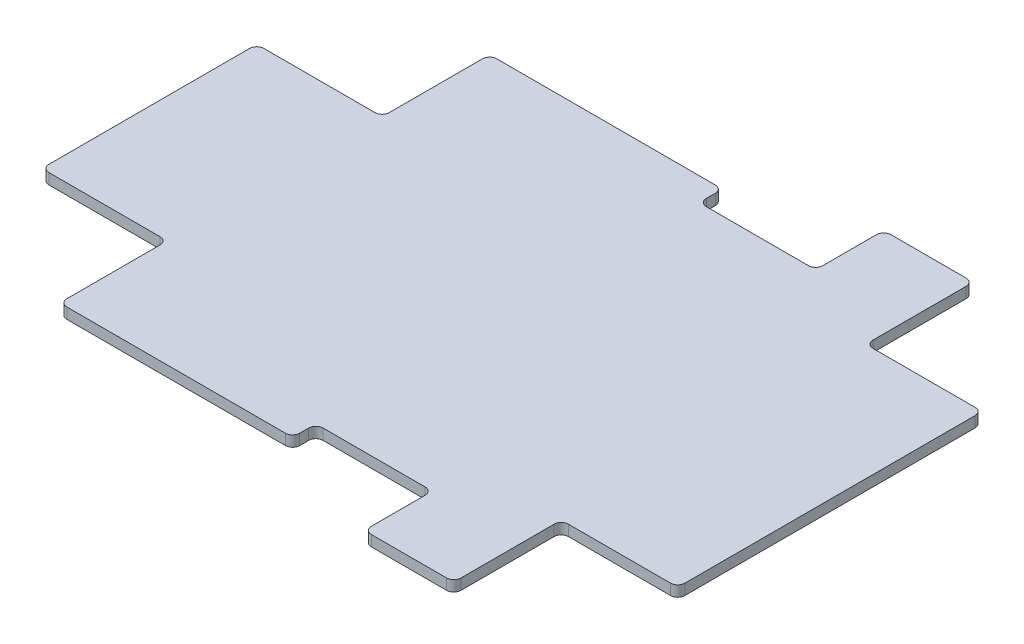
SolidWorks part; units mm, degrees
material "Aleación 1060"
ref_plane "Alzado" through (0, 0, 0) normal (0, 0, 1) x (1, 0, 0)
ref_plane "Planta" through (0, 0, 0) normal (0, 1, 0) x (1, 0, 0)
ref_plane "Vista lateral" through (0, 0, 0) normal (1, 0, 0) x (0, 0, -1)
sketch "Croquis1" plane through (0, 0, 0) normal (0, 1, 0) x (1, 0, 0)
  line L0 (0, 0) -> (-380, 0)
  line L1 (-380, 0) -> (-380, 60)
  line L2 (-380, 60) -> (-310, 60)
  line L3 (-310, 60) -> (-310, 120)
  line L4 (-310, 120) -> (-180, 120)
  line L5 (-180, 120) -> (-180, 107)
  line L6 (-180, 107) -> (-115, 107)
  line L7 (-115, 107) -> (-115, 145)
  line L8 (-115, 145) -> (-65, 145)
  line L9 (-65, 145) -> (-65, 85)
  line L10 (0, 0) -> (0, 85)
  line L11 (0, 85) -> (-65, 85)
  dimension "D1" = 380
  dimension "D2" = 60
  dimension "D3" = 70
  dimension "D4" = 120
  dimension "D5" = 130
  dimension "D6" = 13
  dimension "D7" = 50
  dimension "D8" = 85
  dimension "D9" = 65
  dimension "D10" = 60
extrude "Saliente-Extruir1" add sketch "Croquis1" along normal blind 6
mirror "Simetría1" about plane through (0, 6, 0) normal (0, 0, -1) of "Saliente-Extruir1"
fillet "Redondeo1" radius 4 20 edges at (-380, 3, -60) (-310, 3, -60) (-310, 3, -120) (-180, 3, -120) (-180, 3, -107) (-115, 3, -107) (-115, 3, -145) (-65, 3, -85) (-65, 3, -145) (0, 3, -85) (0, 3, 85) (-65, 3, 85) (-65, 3, 145) (-115, 3, 145) (-115, 3, 107) (-180, 3, 107) (-180, 3, 120) (-310, 3, 120) (-310, 3, 60) (-380, 3, 60)
sketch "Croquis2" plane through (0, 6, 0) normal (0, 1, 0) x (1, 0, 0)
  line L0 (-380, 0) -> (0, 0) construction
  line L1 (-380, 56) -> (-380, -56) construction
  line L2 (0, -81) -> (0, 81) construction
  line L3 (-214.7209, -131) -> (31.1095, -131) construction
  line L4 (-214.0485, -154) -> (44.3152, -154) construction
  line L5 (-69, -145) -> (-111, -145) construction
  line L6 (-34, -177) -> (-146, -177)
  line L7 (-34, -177) -> (-34, -131)
  line L8 (-34, -131) -> (-146, -131)
  line L9 (-146, -177) -> (-146, -131)
  line L10 (-34, -177) -> (-146, -131) construction
  line L11 (-34, -131) -> (-146, -177) construction
  line L13 (-364, -177) -> (-476, -177)
  line L14 (-364, -177) -> (-364, -131)
  line L15 (-364, -131) -> (-476, -131)
  line L16 (-476, -177) -> (-476, -131)
  line L17 (-364, -177) -> (-476, -131) construction
  line L18 (-364, -131) -> (-476, -177) construction
  line L19 (-34, 177) -> (-146, 177)
  line L20 (-34, 177) -> (-34, 131)
  line L21 (-34, 131) -> (-146, 131)
  line L22 (-146, 177) -> (-146, 131)
  line L23 (-364, 131) -> (-476, 177) construction
  line L24 (-364, 177) -> (-476, 131) construction
  line L25 (-476, 177) -> (-476, 131)
  line L26 (-364, 131) -> (-476, 131)
  line L27 (-364, 177) -> (-364, 131)
  line L28 (-364, 177) -> (-476, 177)
  point P10 (-90, -154)
  point P17 (-90, -145)
  point P20 (-420, -154)
  point P33 (-420, 154)
  dimension "D1" = 131
  dimension "D2" = 154
  dimension "D3" = 46
  dimension "D4" = 112
  dimension "D5" = 330
sketch "Croquis3" plane through (0, 6, 0) normal (0, 1, 0) x (1, 0, 0)
  line L0 (-90, -145) -> (-90, 145) construction
  line L1 (-69, -145) -> (-111, -145) construction
  line L2 (-69, 145) -> (-111, 145) construction
  line L3 (-151.61, 16.8885) -> (-151.61, -25.475) construction
  line L4 (-222.2, 27.5722) -> (-222.2, -25.475) construction
  dimension "D1" = 132.2
  dimension "D2" = 61.61
